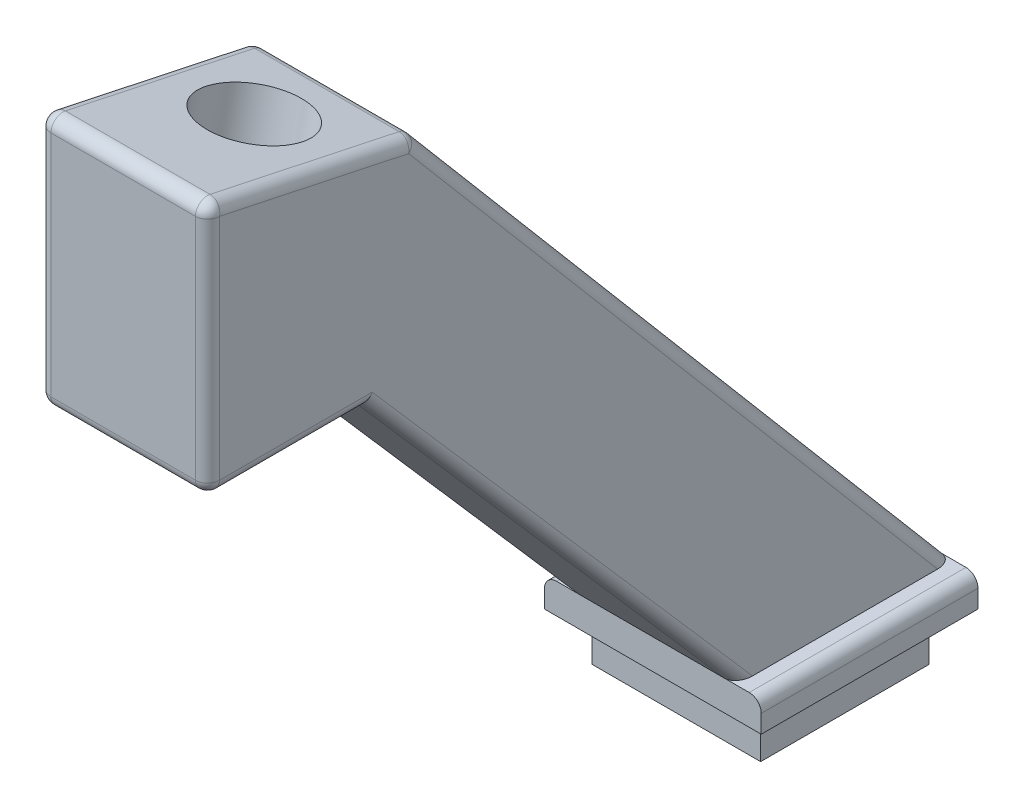
SolidWorks part; units mm, degrees
ref_plane "Front Plane" through (0, 0, 0) normal (0, 0, 1) x (1, 0, 0)
ref_plane "Top Plane" through (0, 0, 0) normal (0, 1, 0) x (1, 0, 0)
ref_plane "Right Plane" through (0, 0, 0) normal (1, 0, 0) x (0, 0, -1)
sketch "Sketch2" plane through (0, 0, 0) normal (0, 1, 0) x (1, 0, 0)
  line L2 (7, 7) -> (-7, 7)
  line L3 (-7, 7) -> (-7, -7)
  line L4 (-7, -7) -> (7, -7)
  line L5 (7, -7) -> (7, 7)
  point P4 (0, 0)
  point P8 (0, 0)
  point P11 (0, 7)
extrude "Boss-Extrude1" add sketch "Sketch2" against normal blind 4 and the other way blind 2.5
sketch "Sketch7" plane through (0, 0, 0) normal (0, 0, 1) x (1, 0, 0)
  line L0 (-6.0346, 0) -> (-4.0346, 0)
  line L2 (0, -33.0044) -> (0, 33.0044) construction
  line L3 (-6.0346, 0) -> (-6.0346, -0.5)
  line L8 (-6.0346, -0.5) -> (-4.0346, -0.5)
  line L9 (-4.0346, -0.5) -> (-4.0346, 0)
  line L10 (4.0346, -0.5) -> (4.0346, 0)
  line L11 (6.0346, -0.5) -> (4.0346, -0.5)
  line L12 (6.0346, 0) -> (6.0346, -0.5)
  line L13 (6.0346, 0) -> (4.0346, 0)
  dimension "D1" = 2
  dimension "D2" = 0.5
sketch "Sketch11" plane through (0, 0, 0) normal (0, 1, 0) x (1, 0, 0)
  line L0 (-8.9488, -8.9993) -> (-8.9488, 9.0007)
  line L1 (-8.9488, 9.0007) -> (9.0512, 9.0007)
  line L2 (-8.9488, -8.9993) -> (9.0512, -8.9993)
  line L3 (9.0512, -8.9993) -> (9.0512, 9.0007)
  dimension "D1" = 18
  dimension "D2" = 18
extrude "Boss-Extrude4" add sketch "Sketch11" along normal blind 2.5
sketch "Sketch3" plane through (0, 0, 0) normal (0, 1, 0) x (1, 0, 0)
  line L0 (2.98, 3.0412) -> (2.98, -2.9588)
  line L2 (2.98, 3.0412) -> (-3.02, 3.0412)
  line L3 (-3.02, 3.0412) -> (-3.02, -2.9588)
  line L4 (-3.02, -2.9588) -> (2.98, -2.9588)
  dimension "D1" = 6
  dimension "D2" = 6
extrude "Cut-Extrude5" cut sketch "Sketch3" against normal blind 4 and the other way blind 4
sketch "Sketch13" plane through (0, 0, 0) normal (1, 0, 0) x (0, 0, -1)
  line L1 (-39.7149, 37.7068) -> (-52.9339, 37.7068)
  line L2 (0, 0) -> (0, 2.5)
  line L3 (0, 2.5) -> (-9, 2.5)
  line L4 (0, 2.5) -> (9, 2.5)
  line L5 (-9, 2.5) -> (-39.7149, 37.7068)
  line L6 (-35.6901, 55.251) -> (9, 2.5)
  line L9 (-52.9339, 37.7068) -> (-52.9339, 58.921)
  line L10 (-52.9339, 58.921) -> (-35.6901, 55.251)
  point P0 (-52.9339, 58.921)
  point P3 (-39.7149, 37.7068)
  point P4 (-35.6901, 55.251)
  point P7 (0, 0)
  point P13 (-36.7284, 50.8414)
  point P15 (-21.6937, 35.8582)
  point P16 (-37.2526, 49.11)
  dimension "D1" = 18
extrude "Boss-Extrude5" add sketch "Sketch13" along normal blind 7 and the other way blind 7 contours L3 L5 L1 L9 L10 L6 L4
sketch "Sketch16" plane through (0, 0, 0) normal (1, 0, 0) x (0, 0, -1)
  line L0 (0, 0) -> (0.0003, 2.5)
  line L1 (-7, 0) -> (7, 0) construction
  line L2 (-8.9993, 2.5) -> (9, 2.5) construction
  line L3 (0.0003, 2.5) -> (3.0014, 2.5)
  line L4 (0.0003, 2.5) -> (-2.9997, 2.5)
  line L5 (-2.9997, 2.5) -> (-42.3379, 42.4659)
  line L6 (-42.3379, 42.4659) -> (-42.3379, 48.4659)
  line L7 (-42.3379, 48.4659) -> (3.0014, 2.5)
  point P6 (-37.659, 38.3202)
  point P12 (-42.3379, 48.4659)
  dimension "D1" = 3
  dimension "D2" = 3.0011
  dimension "D3" = 6
extrude "Cut-Extrude8" cut sketch "Sketch16" against normal blind 3 and the other way blind 3 contours L4 L5 L6 L7 L3
sketch "Sketch52" plane through (0, 0, 0) normal (1, 0, 0) x (0, 0, -1)
  line L0 (-41.0385, 61.3626) -> (-48.8166, 24.8846)
  point P2 (-41.0385, 61.3626)
  point P6 (-41.1515, 60.2248)
sweep "Cut-Sweep4" cut path "Sketch52" circular profile diameter 8 parameters "D3"=8
fillet "Fillet1" radius 1 15 edges at (0, 37.7068, 52.9339) (7, 20.1034, 24.3575) (-8.9488, 2.5, -0.0007) (9.0512, 2.5, -0.0007) (-7, 28.8755, 13.3451) (7, 37.7068, 46.3244) (7, 48.3139, 52.9339) (-7, 48.3139, 52.9339) (-7, 37.7068, 46.3244) (-7, 20.1034, 24.3575) (7, 28.8755, 13.3451) (7, 57.086, 44.312) (0, 58.921, 52.9339) (-7, 57.086, 44.312) (0, 55.251, 35.6901)
